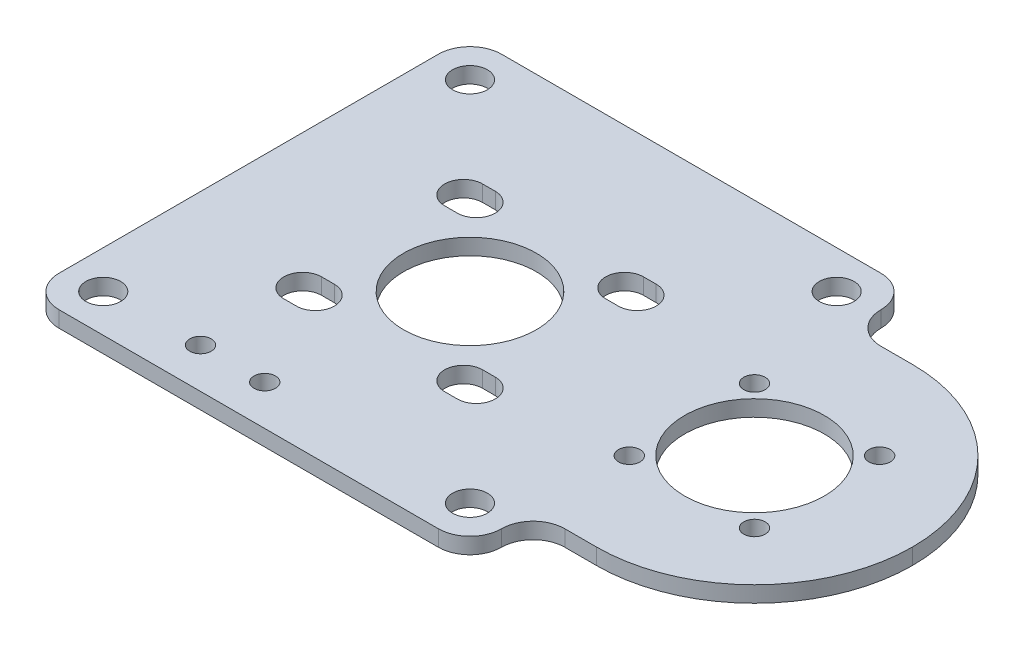
SolidWorks part; units mm, degrees
material "1060 Alloy"
ref_plane "Front Plane" through (0, 0, 0) normal (0, 0, 1) x (1, 0, 0)
ref_plane "Top Plane" through (0, 0, 0) normal (0, 1, 0) x (1, 0, 0)
ref_plane "Right Plane" through (0, 0, 0) normal (1, 0, 0) x (0, 0, -1)
sketch "Sketch1" plane through (0, 0, 0) normal (0, 1, 0) x (1, 0, 0)
  line L0 (0, 0) -> (0, 70)
  line L9 (0, 35) -> (35, 35) construction
  line L10 (35, 35) -> (22.2721, 47.7279) construction
  line L37 (35, 35) -> (35, 53) construction
  line L38 (0, 70) -> (70, 70)
  line L39 (0, 0) -> (70, 0)
  line L41 (80, 35) -> (80, 49) construction
  line L48 (80, 35) -> (70.1005, 44.8995) construction
  line L49 (70, 70) -> (70, 60)
  line L50 (70, 0) -> (70, 10)
  line L51 (70, 60) -> (105, 60)
  line L52 (70, 10) -> (105, 10)
  line L53 (105, 60) -> (105, 10)
  line L54 (21.2721, 47.7279) -> (23.2721, 47.7279) construction
  line L55 (21.2721, 50.7279) -> (23.2721, 50.7279)
  line L56 (21.2721, 44.7279) -> (23.2721, 44.7279)
  line L57 (48.7279, 47.7279) -> (46.7279, 47.7279) construction
  line L58 (48.7279, 50.7279) -> (46.7279, 50.7279)
  line L59 (48.7279, 44.7279) -> (46.7279, 44.7279)
  line L60 (21.2721, 22.2721) -> (23.2721, 22.2721) construction
  line L61 (21.2721, 19.2721) -> (23.2721, 19.2721)
  line L62 (21.2721, 25.2721) -> (23.2721, 25.2721)
  line L63 (48.7279, 22.2721) -> (46.7279, 22.2721) construction
  line L64 (48.7279, 19.2721) -> (46.7279, 19.2721)
  line L65 (48.7279, 25.2721) -> (46.7279, 25.2721)
  line L66 (31.19, 6.35) -> (21.03, 6.35) construction
  line L67 (17.22, 0) -> (35, 0) construction
  line L68 (17.22, 0) -> (17.22, 12.7) construction
  line L69 (17.22, 12.7) -> (35, 12.7) construction
  line L70 (35, 0) -> (35, 12.7) construction
  line L71 (26.11, 12.7) -> (26.11, 0) construction
  circle A19 centre (35, 35) radius 10.5
  circle A20 centre (35, 35) radius 18 construction
  circle A25 centre (80, 35) radius 11.05
  circle A26 centre (80, 35) radius 14 construction
  circle A27 centre (70.1005, 44.8995) radius 1.7
  circle A28 centre (89.8995, 44.8995) radius 1.7
  circle A29 centre (89.8995, 25.1005) radius 1.7
  circle A30 centre (70.1005, 25.1005) radius 1.7
  arc A31 (21.2721, 50.7279) -> (21.2721, 44.7279) centre (21.2721, 47.7279) ccw
  arc A32 (23.2721, 44.7279) -> (23.2721, 50.7279) centre (23.2721, 47.7279) ccw
  arc A33 (48.7279, 50.7279) -> (48.7279, 44.7279) centre (48.7279, 47.7279) cw
  arc A34 (46.7279, 44.7279) -> (46.7279, 50.7279) centre (46.7279, 47.7279) cw
  arc A35 (21.2721, 19.2721) -> (21.2721, 25.2721) centre (21.2721, 22.2721) cw
  arc A36 (23.2721, 25.2721) -> (23.2721, 19.2721) centre (23.2721, 22.2721) cw
  arc A37 (48.7279, 19.2721) -> (48.7279, 25.2721) centre (48.7279, 22.2721) ccw
  arc A38 (46.7279, 25.2721) -> (46.7279, 19.2721) centre (46.7279, 22.2721) ccw
  circle A39 centre (21.03, 6.35) radius 1.7
  circle A40 centre (31.19, 6.35) radius 1.7
  point P6 (18.2721, 47.7279)
  point P14 (26.2721, 47.7279)
  point P21 (47.7279, 47.7279)
  point P23 (35, 35)
  point P39 (80, 35)
  point P42 (22.2721, 47.7279)
  point P52 (22.2721, 22.2721)
  point P60 (47.7279, 22.2721)
  point P74 (26.11, 6.35)
  point P75 (26.11, 6.35)
  dimension "D4" = 36
  dimension "D9" = 28
  dimension "D7" = 70
  dimension "D1" = 70
  dimension "D2" = 35
  dimension "D8" = 22.1
  dimension "D11" = 45
  dimension "D13" = 50
  dimension "D14" = 25
  dimension "D15" = 8
  dimension "D16" = 12.7
  dimension "D3" = 21
  dimension "D6" = 6
  dimension "D12" = 3.4
  dimension "D18" = 3.4
  dimension "D5" = 45
  dimension "D10" = 45
  dimension "D17" = 17.78
  dimension "D19" = 10.16
extrude "Boss-Extrude1" add sketch "Sketch1" along normal blind 2.54
fillet "Fillet1" radius 25 2 edges at (105, 1.27, -10) (105, 1.27, -60)
fillet "Fillet2" radius 5 6 edges at (70, 1.27, -60) (70, 1.27, -10) (0, 1.27, -70) (0, 1.27, 0) (70, 1.27, 0) (70, 1.27, -70)
sketch "Sketch2" plane through (0, 2.54, 0) normal (0, 1, 0) x (1, 0, 0)
  line L0 (0, 65) -> (0, 5) construction
  line L1 (6, 64) -> (64, 64) construction
  line L2 (6, 64) -> (6, 6) construction
  line L3 (6, 6) -> (64, 6) construction
  line L4 (64, 64) -> (64, 6) construction
  line L5 (65, 70) -> (5, 70) construction
  line L6 (5, 0) -> (65, 0) construction
  circle A0 centre (6, 64) radius 2.75
  circle A2 centre (64, 64) radius 2.75
  circle A3 centre (64, 6) radius 2.75
  circle A4 centre (6, 6) radius 2.75
  dimension "D1" = 5.5
  dimension "D2" = 6
  dimension "D3" = 6
  dimension "D4" = 6
extrude "Cut-Extrude1" cut sketch "Sketch2" against normal blind 10
